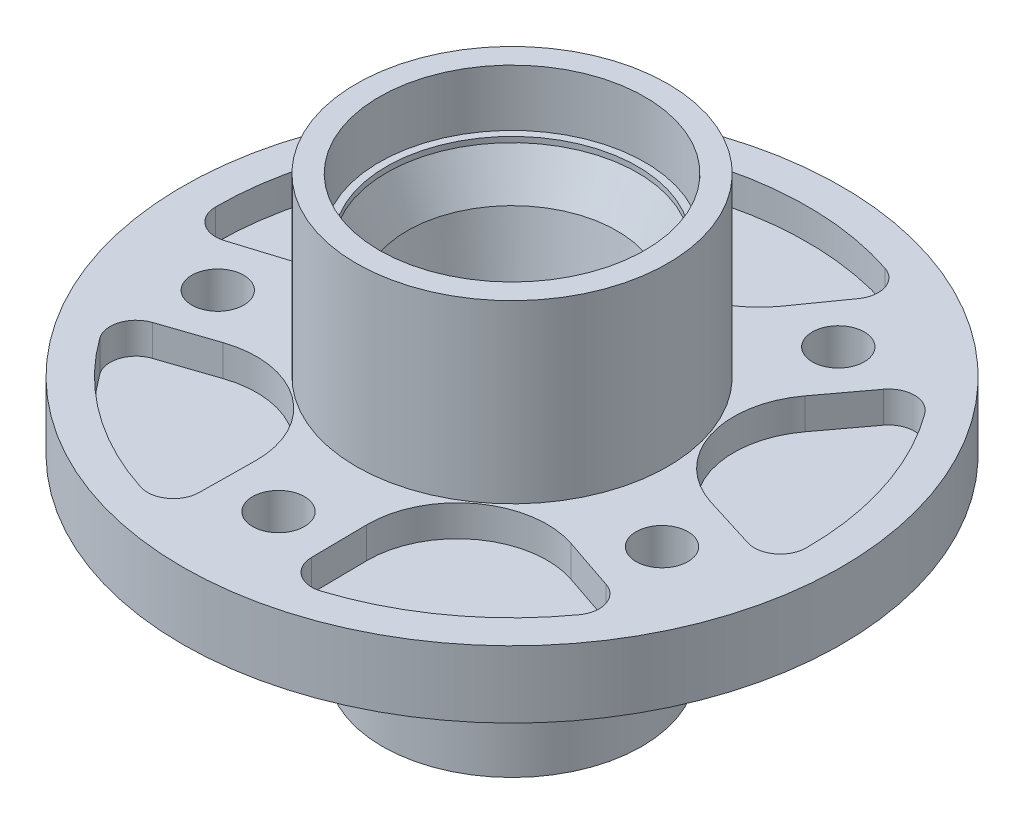
SolidWorks part; units mm, degrees
material "ASTM A36 Steel"
ref_plane "Front Plane" through (0, 0, 0) normal (0, 0, 1) x (1, 0, 0)
ref_plane "Top Plane" through (0, 0, 0) normal (0, 1, 0) x (1, 0, 0)
ref_plane "Right Plane" through (0, 0, 0) normal (1, 0, 0) x (0, 0, -1)
sketch "Sketch1" plane through (0, 0, 0) normal (0, 0, 1) x (1, 0, 0)
  line L0 (0, 66.6082) -> (0, -73.0111) construction
  line L2 (32.512, 43.053) -> (38.1, 43.053)
  line L3 (38.1, 43.053) -> (38.1, 0)
  line L4 (55, 0) -> (-55, 0) construction
  line L5 (38.1, 0) -> (80.645, 0)
  line L6 (80.645, 0) -> (80.645, -16.383)
  line L7 (80.645, -16.383) -> (31.75, -16.383)
  line L8 (31.75, -16.383) -> (31.75, -62.484)
  line L9 (31.75, -62.484) -> (25.146, -62.484)
  line L10 (32.512, 43.053) -> (32.512, 29.21)
  line L11 (32.512, 29.21) -> (30.723, 29.21)
  line L12 (30.723, 29.21) -> (30.723, 27.8812)
  line L13 (30.723, 27.8812) -> (25.6686, 18.1088)
  line L14 (25.6686, 18.1088) -> (26.6046, 18.1088)
  line L15 (26.6046, 18.1088) -> (22.4528, -6.4)
  line L16 (22.4528, -6.4) -> (22.4528, -41.1106)
  line L17 (22.4528, -41.1106) -> (20.298, -41.1106)
  line L18 (20.298, -41.1106) -> (25.146, -49.5775)
  line L21 (25.146, -49.5775) -> (25.146, -62.484)
  dimension "D1" = 76.2
  dimension "D2" = 5.588
  dimension "D3" = 16.383
  dimension "D4" = 63.5
  dimension "D5" = 50.292
  dimension "D6" = 46.101
  dimension "D7" = 161.29
  dimension "D8" = 43.053
  dimension "D9" = 13.843
  dimension "D10" = 12.9065
revolve "Revolve1" add sketch "Sketch1" angle 360 mid plane about L0
sketch "Sketch2" plane through (0, 0, 0) normal (0, 1, 0) x (1, 0, 0)
  circle A0 centre (0, 0) radius 57.15 construction
  circle A1 centre (0, -57.15) radius 6.35
  dimension "D1" = 12.7
  dimension "D2" = 114.3
extrude "Cut-Extrude1" cut sketch "Sketch2" against normal through all
ref_axis "Axis1" through (0, 48.3299, 0) along (0, -1, 0)
pattern_circular "CirPattern1" count 5 over 360 about axis through (0, 48.3299, 0) along (0, -1, 0) of "Cut-Extrude1"
sketch "Sketch3" plane through (0, 0, 0) normal (0, 1, 0) x (1, 0, 0)
  line L0 (-25.8161, 58.9292) -> (-17.9181, 47.7801)
  line L1 (25.8161, 58.9292) -> (17.9181, 47.7801)
  line L2 (0, -58.0453) -> (0, 58.0453) construction
  line L3 (-33.5919, 46.2353) -> (-22.4268, 54.1447) construction
  arc A0 (-22.6224, 68.6307) -> (22.6224, 68.6307) centre (0, 0) cw
  arc A1 (-17.9181, 47.7801) -> (17.9181, 47.7801) centre (0, 60.4733) ccw
  arc A2 (-22.6224, 68.6307) -> (-25.8161, 58.9292) centre (-20.6345, 62.5998) ccw
  arc A3 (22.6224, 68.6307) -> (25.8161, 58.9292) centre (20.6345, 62.5998) cw
  circle A4 centre (0, 0) radius 80.645 construction
  dimension "D1" = 8.382
  dimension "D2" = 6.35
extrude "Cut-Extrude2" cut sketch "Sketch3" against normal blind 7.62
pattern_circular "CirPattern2" count 5 over 360 about axis through (0, 48.3299, 0) along (0, -1, 0) of "Cut-Extrude2"
sketch "Sketch4" plane through (0, -16.383, 0) normal (0, -1, 0) x (1, 0, 0)
  circle A1 centre (0, 0) radius 80.645
  circle A2 centre (0, 0) radius 80.645
  circle A4 centre (-33.5919, -46.2353) radius 6.35 construction
  circle A5 centre (33.5919, -46.2353) radius 6.35 construction
  circle A6 centre (54.3529, 17.6603) radius 6.35 construction
  circle A7 centre (0, 57.15) radius 6.35 construction
  circle A8 centre (-54.3529, 17.6603) radius 6.35 construction
  circle A9 centre (-33.5919, -46.2353) radius 6.35
  circle A10 centre (33.5919, -46.2353) radius 6.35
  circle A11 centre (54.3529, 17.6603) radius 6.35
  circle A12 centre (0, 57.15) radius 6.35
  circle A13 centre (-54.3529, 17.6603) radius 6.35
  dimension "D1" = 0
sketch "Sketch5" plane through (0, -62.484, 0) normal (0, -1, 0) x (1, 0, 0)
  circle A0 centre (0, 0) radius 28.575 construction
  circle A1 centre (0, 28.575) radius 1.1811
  dimension "D1" = 57.15
  dimension "D2" = 2.3622
extrude "Cut-Extrude3" cut sketch "Sketch5" against normal blind 12.7
pattern_circular "CirPattern3" count 6 over 360 about axis through (0, 66.6082, 0) along (0, 1, 0) of "Cut-Extrude3"
